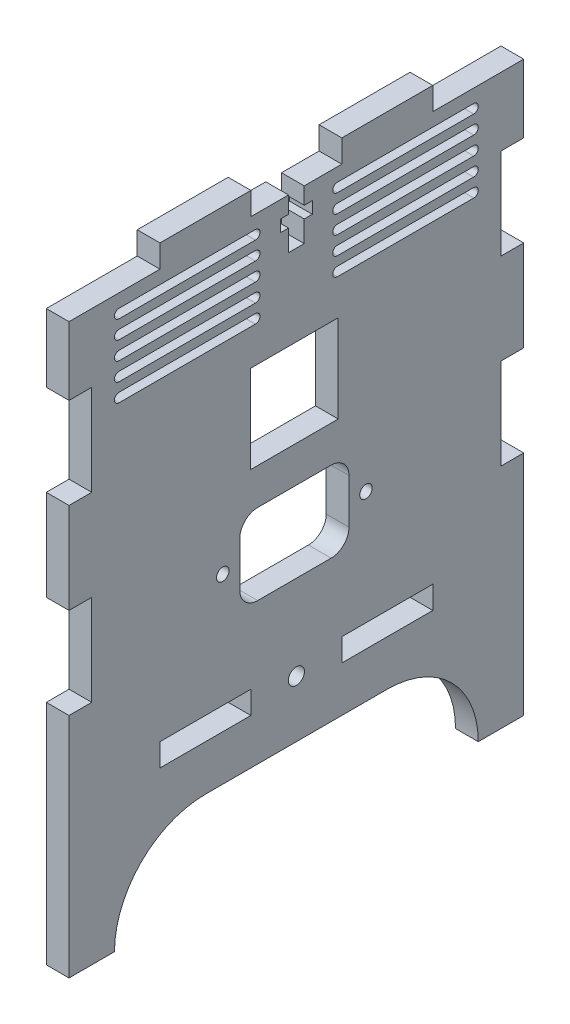
SolidWorks part; units mm, degrees
ref_plane "Front Plane" through (0, 0, 0) normal (0, 0, 1) x (1, 0, 0)
ref_plane "Top Plane" through (0, 0, 0) normal (0, 1, 0) x (1, 0, 0)
ref_plane "Right Plane" through (0, 0, 0) normal (1, 0, 0) x (0, 0, -1)
sketch "Sketch1" plane through (0, 0, 0) normal (1, 0, 0) x (0, 0, -1)
  line L1 (-63.5, 82.55) -> (63.5, 82.55)
  line L2 (-63.5, 82.55) -> (-63.5, -82.55)
  line L3 (-63.5, -82.55) -> (63.5, -82.55)
  line L4 (63.5, 82.55) -> (63.5, -82.55)
  line L5 (-63.5, 82.55) -> (63.5, -82.55) construction
  line L6 (-63.5, -82.55) -> (63.5, 82.55) construction
  point P0 (0, 0)
  dimension "D1" = 127
  dimension "D2" = 165.1
extrude "Boss-Extrude1" add sketch "Sketch1" along normal blind 6.35
sketch "Sketch2" plane through (6.35, 0, 0) normal (1, 0, 0) x (0, 0, -1)
  line L1 (-63.5, 82.55) -> (-38.1, 82.55)
  line L2 (-63.5, 82.55) -> (-63.5, 76.2)
  line L3 (-63.5, 76.2) -> (-38.1, 76.2)
  line L4 (-38.1, 82.55) -> (-38.1, 76.2)
  dimension "D1" = 25.4
  dimension "D2" = 6.35
extrude "Cut-Extrude1" cut sketch "Sketch2" against normal blind 6.35
pattern_linear "LPattern1" count 3 spacing 50.8 along (0, 0, -1) of "Cut-Extrude1"
sketch "Sketch5" plane through (6.35, 0, 0) normal (1, 0, 0) x (0, 0, -1)
  line L0 (-25.4, -82.55) -> (25.4, -82.55) construction
  line L1 (-63.5, -82.55) -> (63.5, -82.55) construction
  line L2 (-25.4, -57.15) -> (25.4, -57.15)
  line L3 (-25.4, -107.95) -> (25.4, -107.95)
  arc A0 (-25.4, -57.15) -> (-25.4, -107.95) centre (-25.4, -82.55) ccw
  arc A1 (25.4, -107.95) -> (25.4, -57.15) centre (25.4, -82.55) ccw
  point P4 (0, -82.55)
  dimension "D2" = 25.4
  dimension "D1" = 50.8
extrude "Cut-Extrude4" cut sketch "Sketch5" against normal blind 6.35
sketch "Sketch8" plane through (6.35, 0, 0) normal (1, 0, 0) x (0, 0, -1)
  line L0 (63.5, -82.55) -> (63.5, 76.2) construction
  line L1 (63.5, 57.15) -> (57.15, 57.15)
  line L2 (63.5, 57.15) -> (63.5, 31.75)
  line L3 (63.5, 31.75) -> (57.15, 31.75)
  line L4 (57.15, 57.15) -> (57.15, 31.75)
  line L5 (38.1, 82.55) -> (12.7, 82.55) construction
  dimension "D1" = 25.4
  dimension "D2" = 25.4
  dimension "D3" = 6.35
extrude "Cut-Extrude6" cut sketch "Sketch8" against normal blind 6.35
pattern_linear "LPattern4" count 2 spacing 50.8 along (0, -1, 0) of "Cut-Extrude6"
ref_plane "Plane1" through (0, 0, 0) normal (0, 0, 1) x (1, 0, 0)
mirror "Mirror1" about plane through (0, 0, 0) normal (0, 0, 1) of "LPattern4"
sketch "Sketch9" plane through (0, 0, 0) normal (-1, 0, 0) x (0, 0, 1)
  line L0 (-63.5, -82.55) -> (-63.5, -19.05) construction
  line L1 (-38.1, -38.1) -> (-12.7, -38.1)
  line L2 (-38.1, -38.1) -> (-38.1, -44.45)
  line L3 (-38.1, -44.45) -> (-12.7, -44.45)
  line L4 (-12.7, -38.1) -> (-12.7, -44.45)
  line L5 (-38.1, 82.55) -> (-12.7, 82.55) construction
  point P6 (-25.4, 82.55)
  dimension "D1" = 25.4
  dimension "D2" = 6.35
  dimension "D3" = 25.4
  dimension "D4" = 120.65
extrude "Cut-Extrude7" cut sketch "Sketch9" against normal blind 6.35
pattern_linear "LPattern6" count 2 spacing 50.8 along (0, 0, 1) of "Cut-Extrude7"
sketch "Sketch16" plane through (0, 0, 0) normal (-1, 0, 0) x (0, 0, 1)
  line L0 (12.7, 76.2) -> (-12.7, 76.2) construction
  line L1 (-2.1971, 76.2) -> (2.1971, 76.2)
  line L2 (-2.1971, 76.2) -> (-2.1971, 62.23)
  line L3 (-2.1971, 62.23) -> (2.1971, 62.23)
  line L4 (2.1971, 76.2) -> (2.1971, 62.23)
  line L5 (-12.7, 76.2) -> (-12.7, 82.55) construction
  line L7 (-4.445, 71.501) -> (4.445, 71.501)
  line L8 (-4.445, 71.501) -> (-4.445, 68.199)
  line L9 (-4.445, 68.199) -> (4.445, 68.199)
  line L10 (4.445, 71.501) -> (4.445, 68.199)
  point P6 (0, 62.23)
  point P13 (0, 71.501)
  point P14 (4.445, 69.85)
  dimension "D1" = 4.3942
  dimension "D2" = 13.97
  dimension "D3" = 12.7
  dimension "D4" = 3.302
  dimension "D5" = 8.89
  dimension "D6" = 12.7
  dimension "D7" = 6.35
extrude "Cut-Extrude14" cut sketch "Sketch16" against normal blind 6.35 contours L7 L10 L9 L8 | L1 L4 L3 L2
hole_wizard "#8 Clearance Hole1" positions "Sketch18" profile "Sketch17" hole size "#8" standard "ANSI Inch"
sketch "Sketch18" plane through (0, 0, 0) normal (-1, 0, 0) x (0, 0, 1)
  line L3 (-12.7, -44.45) -> (-12.7, -38.1) construction
  line L4 (38.1, -38.1) -> (12.7, -38.1) construction
  point P0 (0, -41.275)
  point P16 (-12.7, -41.275)
  dimension "D1" = 12.7
  dimension "D2" = 3.175
sketch "Sketch17" plane through (0, -41.275, 0) normal (0, 1, 0) x (0, 0, 1)
  line L0 (0, 0) -> (0, 11.5107)
  line L1 (0, 11.5107) -> (2.2479, 10.16)
  line L2 (2.2479, 10.16) -> (2.2479, 0)
  line L5 (2.2479, 0) -> (0, 0)
  line L10 (0, 11.5107) -> (-2.2479, 10.16) construction
  line L11 (0, -6.35) -> (0, 107.95) construction
  dimension "Hole Dia." = 4.4958
  dimension "Hole Depth" = 10.16
  dimension "Drill Angle" = 118
sketch "Sketch19" plane through (0, 0, 0) normal (-1, 0, 0) x (0, 0, 1)
  line L0 (-49.53, 71.1789) -> (-11.43, 71.1789) construction
  line L1 (-49.53, 72.4489) -> (-11.43, 72.4489)
  line L2 (-49.53, 69.9089) -> (-11.43, 69.9089)
  line L3 (-38.1, 82.55) -> (-38.1, 76.2) construction
  arc A0 (-49.53, 72.4489) -> (-49.53, 69.9089) centre (-49.53, 71.1789) ccw
  arc A1 (-11.43, 69.9089) -> (-11.43, 72.4489) centre (-11.43, 71.1789) ccw
  point P2 (-30.48, 71.1789)
  point P7 (-30.48, 72.4489)
  dimension "D2" = 1.27
  dimension "D1" = 38.1
  dimension "D3" = 7.62
extrude "Cut-Extrude15" cut sketch "Sketch19" against normal blind 6.35
mirror "Mirror2" about plane through (0, 0, 0) normal (0, 0, 1) of "Cut-Extrude15"
pattern_linear "LPattern7" count 5 spacing 5.08 along (0, -1, 0) of "Mirror2"
sketch "Sketch20" plane through (0, 0, 0) normal (-1, 0, 0) x (0, 0, 1)
  line L0 (57.15, 6.35) -> (57.15, -19.05) construction
  line L1 (-9.6925, 4.9) -> (10.8075, 4.9)
  line L2 (-14.6925, -0.1) -> (-14.6925, -12.6)
  line L3 (-9.6925, -17.6) -> (10.8075, -17.6)
  line L4 (15.8075, -0.1) -> (15.8075, -12.6)
  circle A0 centre (-19.4425, -6.35) radius 1.75
  circle A1 centre (20.5575, -6.35) radius 1.75
  arc A2 (-14.6925, -12.6) -> (-9.6925, -17.6) centre (-9.6925, -12.6) ccw
  arc A3 (10.8075, 4.9) -> (15.8075, -0.1) centre (10.8075, -0.1) cw
  arc A4 (10.8075, -17.6) -> (15.8075, -12.6) centre (10.8075, -12.6) ccw
  arc A5 (-14.6925, -0.1) -> (-9.6925, 4.9) centre (-9.6925, -0.1) cw
  point P8 (15.8075, -6.35)
  point P9 (0.5575, 4.9)
  point P12 (57.15, -6.35)
  point P13 (-14.6925, -6.35)
  point P18 (15.8075, 4.9)
  point P21 (15.8075, -17.6)
  point P24 (-14.6925, 4.9)
  dimension "D1" = 3.5
  dimension "D2" = 3.5
  dimension "D10" = 5
  dimension "D11" = 5
  dimension "D12" = 5
  dimension "D13" = 5
  dimension "D3" = 40
  dimension "D4" = 30.5
  dimension "D5" = 22.5
  dimension "D6" = 0
  dimension "D7" = 20
  dimension "D8" = 0
extrude "Cut-Extrude16" cut sketch "Sketch20" against normal blind 7.62
sketch "Sketch22" plane through (0, 0, 0) normal (-1, 0, 0) x (0, 0, 1)
  line L0 (10.8075, 4.9) -> (-9.6925, 4.9) construction
  line L1 (-11.6925, 39.56) -> (12.8075, 39.56)
  line L2 (-11.6925, 39.56) -> (-11.6925, 15.06)
  line L3 (-11.6925, 15.06) -> (12.8075, 15.06)
  line L4 (12.8075, 39.56) -> (12.8075, 15.06)
  point P4 (0.5575, 15.06)
  point P5 (0.5575, 4.9)
  dimension "D1" = 24.5
  dimension "D2" = 24.5
  dimension "D3" = 0
  dimension "D4" = 10.16
extrude "Cut-Extrude17" cut sketch "Sketch22" against normal blind 6.35
